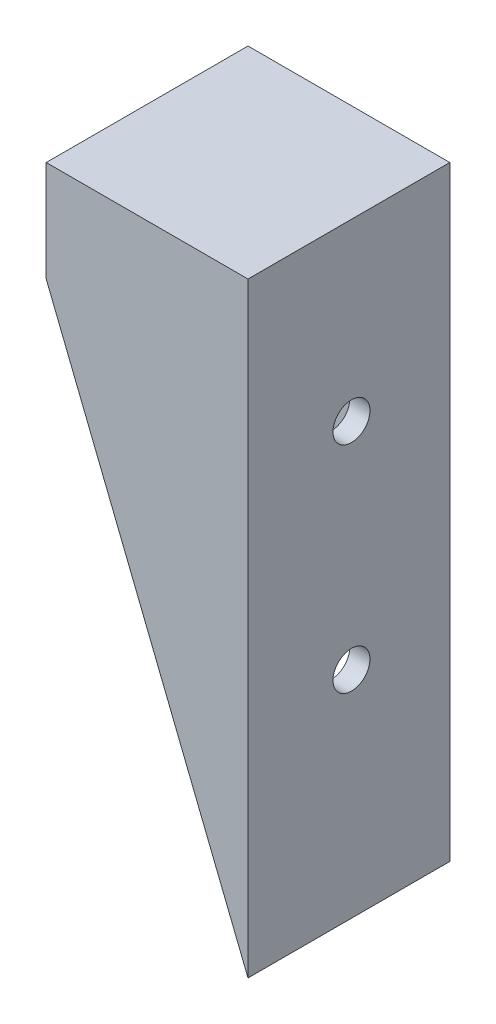
SolidWorks part; units mm, degrees
ref_plane "前基準面" through (0, 0, 0) normal (0, 0, 1) x (1, 0, 0)
ref_plane "上基準面" through (0, 0, 0) normal (0, 1, 0) x (1, 0, 0)
ref_plane "右基準面" through (0, 0, 0) normal (1, 0, 0) x (0, 0, -1)
sketch "草圖1" plane through (0, 0, 0) normal (0, 0, 1) x (1, 0, 0)
  line L0 (-18.9403, 5.5686) -> (11.0597, -69.4314)
  line L1 (-18.9403, 20.5686) -> (11.0597, 20.5686)
  line L2 (-18.9403, 20.5686) -> (-18.9403, 5.5686)
  line L4 (11.0597, 20.5686) -> (11.0597, -69.4314)
  dimension "D1" = 15
  dimension "D2" = 30
  dimension "D3" = 90
extrude "填料-伸長1" add sketch "草圖1" along normal blind 30
sketch "草圖2" plane through (-18.9403, 0, 0) normal (-1, 0, 0) x (0, 0, 1)
  line L0 (30, 5.5686) -> (30, -69.4314) construction
  line L1 (5, 1.8713) -> (25, 1.8713)
  line L2 (5, 1.8713) -> (5, -48.1287)
  line L3 (5, -48.1287) -> (25, -48.1287)
  line L4 (25, 1.8713) -> (25, -48.1287)
  line L5 (0, 5.5686) -> (0, -69.4314) construction
  line L6 (30, 5.5686) -> (0, 5.5686) construction
  dimension "D1" = 5
  dimension "D2" = 5
  dimension "D3" = 50
  dimension "D4" = 3.6972
extrude "除料-伸長1" cut sketch "草圖2" against normal blind 27
sketch "草圖3" plane through (8.0597, 0, 0) normal (-1, 0, 0) x (0, 0, 1)
  line L0 (30, 5.5686) -> (30, -69.4314) construction
  line L1 (30, 20.5686) -> (0, 20.5686) construction
  circle A0 centre (14.6169, -5.4314) radius 2.75
  circle A1 centre (14.6169, -37.4314) radius 2.75
  dimension "D1" = 5.5
  dimension "D4" = 5.5
  dimension "D2" = 15.3831
  dimension "D3" = 26
  dimension "D5" = 32
extrude "除料-伸長2" cut sketch "草圖3" against normal through all
